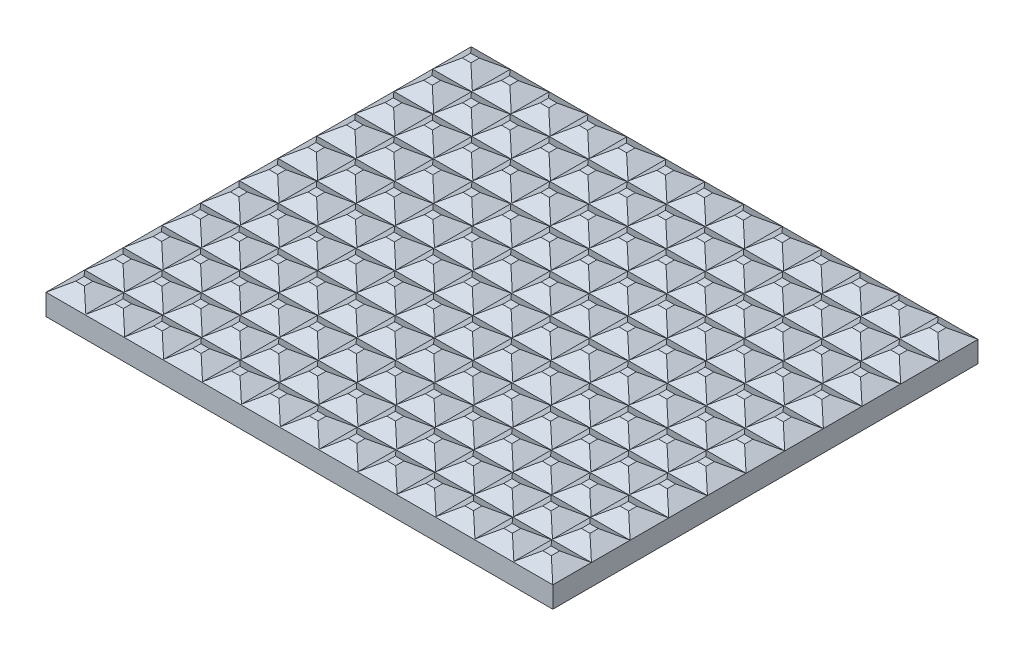
SolidWorks part; units mm, degrees
material "ABS"
ref_plane "Front Plane" through (0, 0, 0) normal (0, 0, 1) x (1, 0, 0)
ref_plane "Top Plane" through (0, 0, 0) normal (0, 1, 0) x (1, 0, 0)
ref_plane "Right Plane" through (0, 0, 0) normal (1, 0, 0) x (0, 0, -1)
sketch "Sketch1" plane through (0, 0, 0) normal (0, 1, 0) x (1, 0, 0)
  line L6 (-29.5, 24.75) -> (29.5, 24.75)
  line L28 (-29.5, 24.75) -> (-29.5, -24.75)
  line L29 (-29.5, -24.75) -> (29.5, -24.75)
  line L30 (29.5, 24.75) -> (29.5, -24.75)
  line L31 (-29.5, 24.75) -> (29.5, -24.75) construction
  line L32 (-29.5, -24.75) -> (29.5, 24.75) construction
  circle A1 centre (0, 0) radius 3
  point P0 (0, 0)
  dimension "D3" = 6
  dimension "D1" = 59
  dimension "D2" = 49.5
extrude "Boss-Extrude1" add sketch "Sketch1" along normal blind 1.5
sketch "Sketch2" plane through (0, 0, -24.75) normal (0, 0, -1) x (-1, 0, 0)
  line L0 (2.265, 2.5) -> (4.53, 4)
  line L1 (-29.5, 1.5) -> (29.5, 1.5)
  line L4 (29.5, 1.5) -> (29.5, 2.4636)
  line L6 (4.53, 4) -> (6.795, 2.5)
  line L56 (-2.265, 2.5) -> (0, 4)
  line L57 (0, 4) -> (2.265, 2.5)
  line L58 (-29.5, 1.5) -> (29.5, 1.5) construction
  line L59 (-29.5, 1.5) -> (-29.5, 2.4636)
  line L60 (6.795, 2.5) -> (9.06, 4)
  line L61 (9.06, 4) -> (11.325, 2.5)
  line L62 (11.325, 2.5) -> (13.59, 4)
  line L63 (13.59, 4) -> (15.855, 2.5)
  line L64 (15.855, 2.5) -> (18.12, 4)
  line L65 (18.12, 4) -> (20.385, 2.5)
  line L66 (20.385, 2.5) -> (22.65, 4)
  line L67 (22.65, 4) -> (24.915, 2.5)
  line L68 (24.915, 2.5) -> (27.18, 4)
  line L69 (27.18, 4) -> (29.445, 2.5)
  line L70 (29.445, 2.5) -> (29.5, 2.4636)
  line L71 (0, 0.825) -> (0, -0.825) construction
  line L72 (-29.445, 2.5) -> (-29.5, 2.4636)
  line L73 (-27.18, 4) -> (-29.445, 2.5)
  line L74 (-24.915, 2.5) -> (-27.18, 4)
  line L75 (-22.65, 4) -> (-24.915, 2.5)
  line L76 (-20.385, 2.5) -> (-22.65, 4)
  line L77 (-18.12, 4) -> (-20.385, 2.5)
  line L78 (-15.855, 2.5) -> (-18.12, 4)
  line L79 (-13.59, 4) -> (-15.855, 2.5)
  line L80 (-11.325, 2.5) -> (-13.59, 4)
  line L81 (-9.06, 4) -> (-11.325, 2.5)
  line L82 (-6.795, 2.5) -> (-9.06, 4)
  line L83 (-4.53, 4) -> (-6.795, 2.5)
  line L84 (-2.265, 2.5) -> (-4.53, 4)
  dimension "D1" = 7
  dimension "D2" = 1.5
  dimension "D3" = 4.53
extrude "Boss-Extrude2" add sketch "Sketch2" against normal up to surface (49.5 mm away) up to face at (0, 0.75, 24.75)
sketch "Sketch3" plane through (0, 0, 0) normal (0, -1, 0) x (-1, 0, 0)
  line L0 (0, 0.825) -> (0, -0.825) construction
  line L2 (-1.75, -2.4367) -> (-1.75, -5)
  line L3 (-1.75, -5) -> (1.75, -5)
  line L4 (1.75, -2.4367) -> (1.75, -5)
  arc A0 (1.75, -2.4367) -> (-1.75, -2.4367) centre (0, 0) ccw
  dimension "D2" = 6
  dimension "D1" = 3.5
  dimension "D3" = 5
  dimension "D4" = 1.75
extrude "Cut-Extrude1" cut sketch "Sketch3" against normal blind 1
sketch "Sketch5" plane through (0, 1.5, 0) normal (0, -1, 0) x (1, 0, 0)
  circle A0 centre (0, 0) radius 3
  dimension "D1" = 6
extrude "Boss-Extrude3" add sketch "Sketch5" along normal blind 0.5
sketch "Sketch6" plane through (0, 1, 0) normal (0, -1, 0) x (1, 0, 0)
  line L1 (1.75, 5) -> (-1.75, 5)
  line L2 (1.75, 5) -> (1.75, 2.4367)
  line L3 (1.75, 2.4367) -> (-1.75, 2.4367)
  line L4 (-1.75, 5) -> (-1.75, 2.4367)
extrude "Cut-Extrude4" cut sketch "Sketch6" against normal blind 0.5
chamfer "Chamfer3" distance 1.5 angle 45 1 edges at (0, 0, 5)
sketch "Sketch9" plane through (29.5, 0, 0) normal (1, 0, 0) x (0, 0, -1)
  line L53 (-24.75, 2.4636) -> (-22.65, 4)
  line L55 (-22.65, 4) -> (-20.25, 2.4636)
  line L57 (-20.25, 2.4636) -> (-18.15, 4)
  line L58 (-18.15, 4) -> (-15.75, 2.4636)
  line L59 (-15.75, 2.4636) -> (-13.65, 4)
  line L60 (-13.65, 4) -> (-11.25, 2.4636)
  line L61 (-11.25, 2.4636) -> (-9.15, 4)
  line L62 (-9.15, 4) -> (-6.75, 2.4636)
  line L63 (-6.75, 2.4636) -> (-4.65, 4)
  line L64 (-4.65, 4) -> (-2.25, 2.4636)
  line L65 (-2.25, 2.4636) -> (-0.15, 4)
  line L66 (-0.15, 4) -> (2.25, 2.4636)
  line L67 (2.25, 2.4636) -> (4.35, 4)
  line L68 (4.35, 4) -> (6.75, 2.4636)
  line L69 (6.75, 2.4636) -> (8.85, 4)
  line L70 (8.85, 4) -> (11.25, 2.4636)
  line L71 (11.25, 2.4636) -> (13.35, 4)
  line L72 (13.35, 4) -> (15.75, 2.4636)
  line L73 (15.75, 2.4636) -> (17.85, 4)
  line L74 (17.85, 4) -> (20.25, 2.4636)
  line L75 (20.25, 2.4636) -> (22.35, 4)
  line L76 (22.35, 4) -> (24.75, 2.4636)
  line L97 (-24.75, 2.4636) -> (-24.75, 6.4088)
  line L98 (-24.75, 6.4088) -> (24.75, 6.4088)
  line L100 (-24.75, 4) -> (24.75, 4) construction
  line L102 (-24.75, 2.4636) -> (-24.75, 4) construction
  line L103 (24.75, 2.4636) -> (24.75, 6.4088)
  line L105 (24.75, 2.4636) -> (26.85, 4) [skipped]
  line L106 (26.85, 4) -> (29.25, 2.4636) [skipped]
  line L107 (29.25, 2.4636) -> (31.35, 4) [skipped]
  line L108 (31.35, 4) -> (33.75, 2.4636) [skipped]
  line L109 (33.75, 2.4636) -> (35.85, 4) [skipped]
  line L110 (35.85, 4) -> (38.25, 2.4636) [skipped]
  line L111 (38.25, 2.4636) -> (40.35, 4) [skipped]
  line L112 (40.35, 4) -> (42.75, 2.4636) [skipped]
  line L113 (42.75, 2.4636) -> (44.85, 4) [skipped]
  line L114 (44.85, 4) -> (47.25, 2.4636) [skipped]
  line L115 (47.25, 2.4636) -> (49.35, 4) [skipped]
  line L116 (49.35, 4) -> (51.75, 2.4636) [skipped]
  line L117 (51.75, 2.4636) -> (53.85, 4) [skipped]
  line L118 (53.85, 4) -> (56.25, 2.4636) [skipped]
  line L119 (56.25, 2.4636) -> (58.35, 4) [skipped]
  line L120 (58.35, 4) -> (60.75, 2.4636) [skipped]
  line L121 (60.75, 2.4636) -> (62.85, 4) [skipped]
  line L122 (62.85, 4) -> (65.25, 2.4636) [skipped]
  line L123 (65.25, 2.4636) -> (67.35, 4) [skipped]
  line L124 (67.35, 4) -> (69.75, 2.4636) [skipped]
  dimension "D3" = 4.5
  dimension "D4" = 2.1
  dimension "D5" = 21
extrude "Cut-Extrude6" cut sketch "Sketch9" against normal through all
sketch "Sketch10" plane through (0, 0, 0) normal (0, 0, 1) x (1, 0, 0)
  line L0 (27.18, 4) -> (29.5, 2.4636) construction
  line L1 (31.1569, 5.8692) -> (-31.5744, 5.8692)
  line L2 (31.1569, 5.8692) -> (31.1569, 3.6689)
  line L3 (31.1569, 3.6689) -> (-31.5744, 3.6689)
  line L4 (-31.5744, 5.8692) -> (-31.5744, 3.6689)
  line L5 (24.915, 2.5) -> (27.18, 4) construction
  point P4 (27.68, 3.6689)
  point P8 (26.68, 3.6689)
  dimension "D1" = 1
extrude "Cut-Extrude7" cut sketch "Sketch10" against normal through all both and the other way through all
